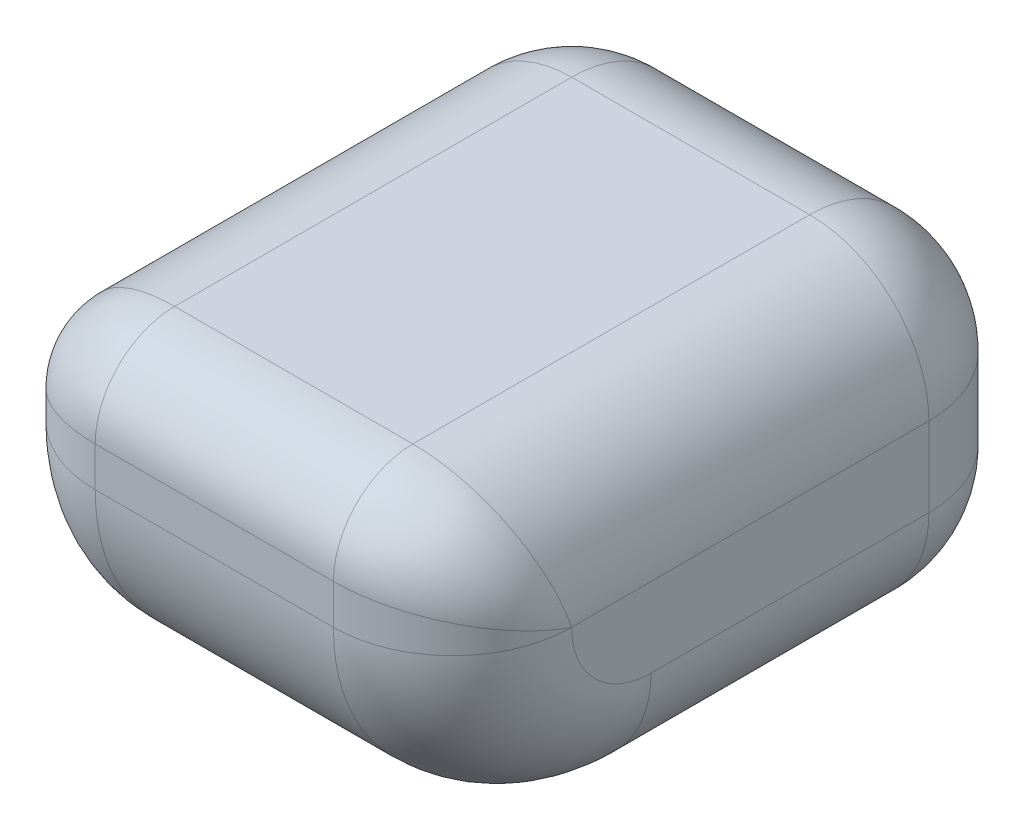
SolidWorks part; units mm, degrees
material "NEOPRENE"
ref_plane "Front Plane" through (0, 0, 0) normal (0, 0, 1) x (1, 0, 0)
ref_plane "Top Plane" through (0, 0, 0) normal (0, 1, 0) x (1, 0, 0)
ref_plane "Right Plane" through (0, 0, 0) normal (1, 0, 0) x (0, 0, -1)
sketch "Sketch1" plane through (0, 0, 0) normal (0, 0, 1) x (1, 0, 0)
  line L1 (-130.6376, 83.5107) -> (174.1624, 83.5107)
  line L2 (-130.6376, 83.5107) -> (-130.6376, -119.6893)
  line L3 (-130.6376, -119.6893) -> (174.1624, -119.6893)
  line L4 (174.1624, 83.5107) -> (174.1624, -119.6893)
  dimension "D1" = 304.8
  dimension "D2" = 203.2
extrude "Boss-Extrude1" add sketch "Sketch1" along normal blind 304.8
fillet "Fillet2" radius 127 1 edges at (21.7624, -119.6893, 304.8)
fillet "Fillet3" radius 50.8 1 edges at (21.7624, 83.5107, 304.8)
fillet "Fillet4" radius 76.2 10 edges at (174.1624, -119.6893, 88.9) (174.1624, -82.4919, 267.6026) (174.1624, 20.0107, 304.8) (174.1624, 68.6317, 289.921) (-130.6376, -119.6893, 88.9) (-130.6376, -82.4919, 267.6026) (-130.6376, 20.0107, 304.8) (-130.6376, 68.6317, 289.921) (174.1624, 83.5107, 127) (-130.6376, 83.5107, 127)
sketch "Sketch2" plane through (0, 0, 0) normal (0, 0, -1) x (-1, 0, 0)
  point P0 (-21.7624, -18.0893)
sketch "Sketch3" plane through (0, 0, 0) normal (0, 0, -1) x (-1, 0, 0)
  line L4 (-174.1624, 7.3107) -> (-174.1624, -43.4893)
  line L5 (-97.9624, -119.6893) -> (54.4376, -119.6893)
  line L6 (130.6376, -43.4893) -> (130.6376, 7.3107)
  line L7 (54.4376, 83.5107) -> (-97.9624, 83.5107)
  line L8 (-174.1624, 7.3107) -> (-174.1624, -43.4893)
  line L9 (-97.9624, -119.6893) -> (54.4376, -119.6893)
  line L10 (130.6376, -43.4893) -> (130.6376, 7.3107)
  line L11 (54.4376, 83.5107) -> (-97.9624, 83.5107)
  arc A4 (-174.1624, -43.4893) -> (-97.9624, -119.6893) centre (-97.9624, -43.4893) ccw
  arc A5 (54.4376, -119.6893) -> (130.6376, -43.4893) centre (54.4376, -43.4893) ccw
  arc A6 (130.6376, 7.3107) -> (54.4376, 83.5107) centre (54.4376, 7.3107) ccw
  arc A7 (-97.9624, 83.5107) -> (-174.1624, 7.3107) centre (-97.9624, 7.3107) ccw
  arc A8 (-174.1624, -43.4893) -> (-97.9624, -119.6893) centre (-97.9624, -43.4893) ccw
  arc A9 (54.4376, -119.6893) -> (130.6376, -43.4893) centre (54.4376, -43.4893) ccw
  arc A10 (130.6376, 7.3107) -> (54.4376, 83.5107) centre (54.4376, 7.3107) ccw
  arc A11 (-97.9624, 83.5107) -> (-174.1624, 7.3107) centre (-97.9624, 7.3107) ccw
  dimension "D1" = 0
extrude "Boss-Extrude2" add sketch "Sketch3" along normal blind 76.2
fillet "Fillet5" radius 76.2 8 edges at (21.7624, 83.5107, -76.2) (-108.3192, 61.1922, -76.2) (-130.6376, -18.0893, -76.2) (-108.3192, -97.3708, -76.2) (21.7624, -119.6893, -76.2) (151.8439, -97.3708, -76.2) (174.1624, -18.0893, -76.2) (151.8439, 61.1922, -76.2)
ref_plane "Plane1" through (0, -18.0893, 0) normal (0, 1, 0) x (1, 0, 0)
sketch "Sketch4" plane through (0, -18.0893, 0) normal (0, 1, 0) x (1, 0, 0)
  line L0 (-130.6376, 0) -> (174.1624, 0)
  arc A0 (174.1624, 0) -> (97.9624, 76.2) centre (97.9624, 0) ccw construction
ref_plane "Plane2" through (-41.7376, 0, 0) normal (-1, 0, 0) x (0, 0, 1)
sketch "Sketch5" plane through (-41.7376, 0, 0) normal (-1, 0, 0) x (0, 0, 1)
  line L1 (304.8, 32.7107) -> (304.8, 7.3107) construction
  line L2 (0, 83.5107) -> (254, 83.5107) construction
  point P0 (215.9, -5.3893)
  dimension "D1" = 88.9
  dimension "D2" = 88.9
ref_plane "Plane3" through (85.2624, 0, 0) normal (1, 0, 0) x (0, 0, -1)
sketch "Sketch6" plane through (85.2624, 0, 0) normal (1, 0, 0) x (0, 0, -1)
  line L0 (-254, 83.5107) -> (0, 83.5107) construction
  line L1 (-304.8, 7.3107) -> (-304.8, 32.7107) construction
  point P0 (-215.9, -5.3893)
  dimension "D1" = 88.9
  dimension "D2" = 88.9
sketch3d "3DSketch1"
  line L0 (-41.7376, -5.3893, 215.9) -> (85.2624, -5.3893, 215.9)
  line L1 (21.7624, -18.0893, 0) -> (21.7624, -5.3893, 215.9)
